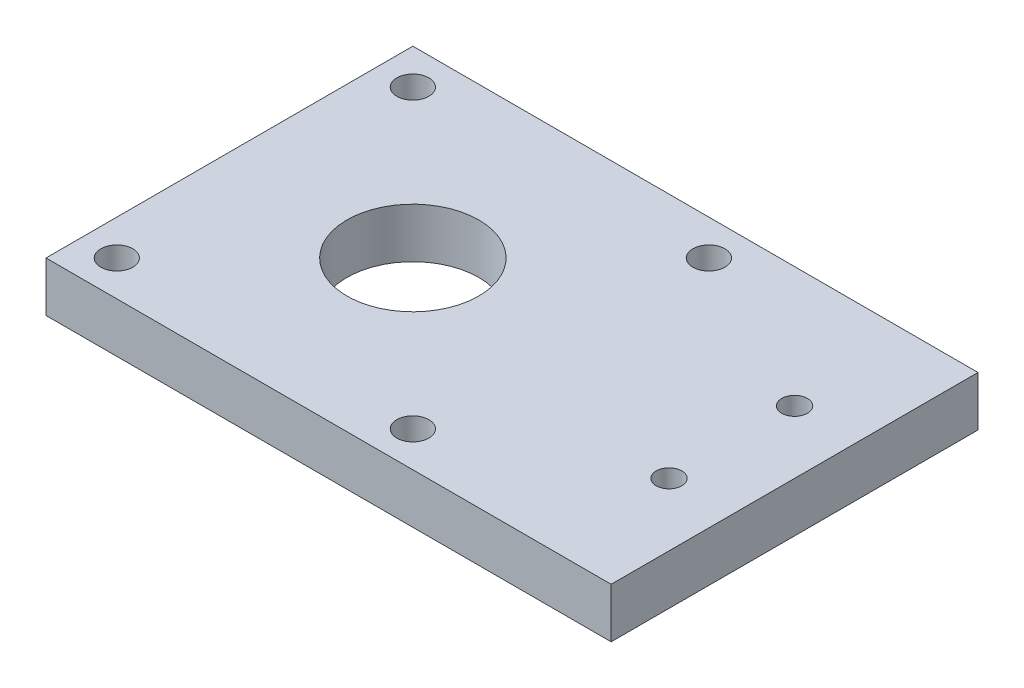
SolidWorks part; units mm, degrees
ref_plane "Top Plane" through (0, 0, 0) normal (0, 0, 1) x (1, 0, 0)
ref_plane "Front Plane" through (0, 0, 0) normal (0, 1, 0) x (1, 0, 0)
ref_plane "Right Plane" through (0, 0, 0) normal (1, 0, 0) x (0, 0, -1)
sketch "Sketch1" plane through (0, -110.0687, 0) normal (0, -1, 0) x (1, 0, 0)
  line L0 (75.5067, 81.6091) -> (75.5067, 61.6091) construction
  line L1 (-4.4933, 100.8191) -> (85.5067, 100.8191)
  line L2 (-4.4933, 100.8191) -> (-4.4933, 42.3991)
  line L3 (-4.4933, 42.3991) -> (85.5067, 42.3991)
  line L4 (85.5067, 100.8191) -> (85.5067, 42.3991)
  circle A0 centre (1.1467, 95.1791) radius 2.55
  circle A1 centre (1.1467, 48.0391) radius 2.55
  circle A2 centre (48.2867, 48.0391) radius 2.55
  circle A3 centre (48.2867, 95.1791) radius 2.55
  circle A4 centre (1.1467, 95.1791) radius 2.1 construction
  circle A5 centre (1.1467, 48.0391) radius 2.1 construction
  circle A6 centre (48.2867, 48.0391) radius 2.1 construction
  circle A7 centre (48.2867, 95.1791) radius 2.1 construction
  circle A10 centre (75.5067, 81.6091) radius 2.05
  circle A11 centre (75.5067, 61.6091) radius 2.05
  circle A14 centre (24.7167, 71.6091) radius 10.5
  circle A15 centre (24.7167, 71.6091) radius 10.5
  point P22 (85.5067, 85.0229)
  point P29 (-4.4933, 71.6091)
  point P30 (75.5067, 71.6091)
  point P47 (77.5995, 52.113)
  dimension "D1" = 5.1
  dimension "D2" = 4.1
  dimension "D3" = 20
  dimension "D4" = 90
  dimension "D5" = 10
  dimension "D6" = 0.5
extrude "Boss-Extrude1" add sketch "Sketch1" along normal blind 7.9375
ref_plane "Plane1" through (0, -114.0374, 0) normal (0, -1, 0) x (-1, 0, 0)
